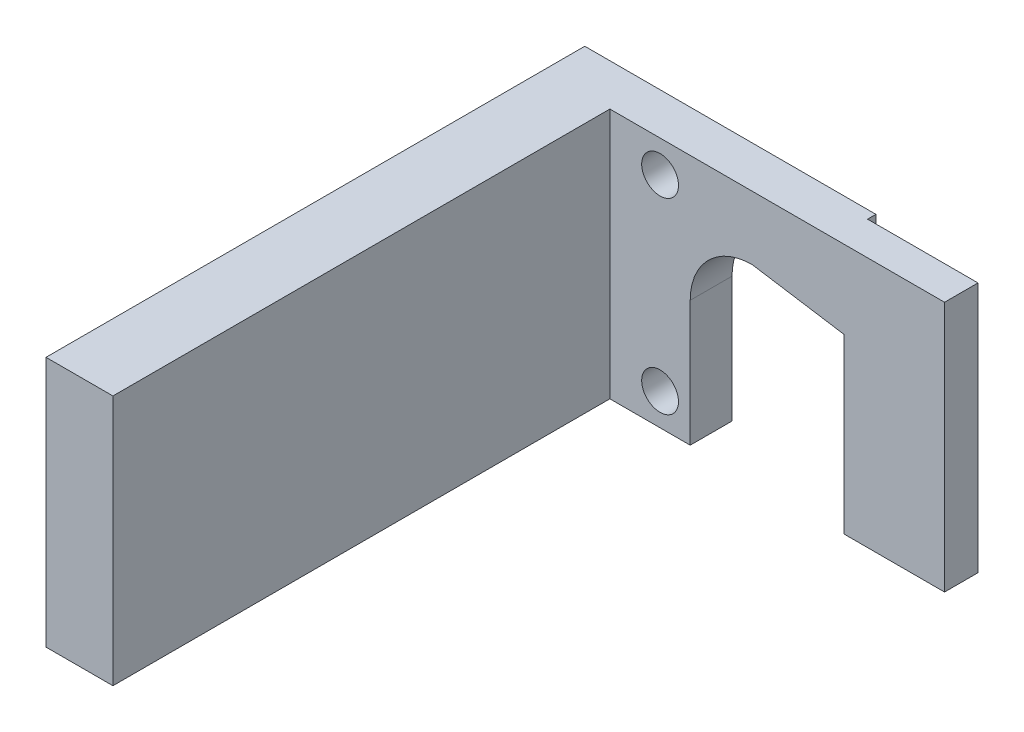
SolidWorks part; units mm, degrees
ref_plane "Front Plane" through (0, 0, 0) normal (0, 0, 1) x (1, 0, 0)
ref_plane "Top Plane" through (0, 0, 0) normal (0, 1, 0) x (1, 0, 0)
ref_plane "Right Plane" through (0, 0, 0) normal (1, 0, 0) x (0, 0, -1)
sketch "Sketch1" plane through (0, 0, 0) normal (0, 0, 1) x (1, 0, 0)
  line L0 (30.48, 9.398) -> (1.27, 9.398) construction
  line L1 (-8.128, 0) -> (-8.128, -19.05)
  line L2 (-30.48, -19.05) -> (-8.128, -19.05)
  line L3 (-30.48, -19.05) -> (-30.48, 19.05)
  line L4 (-30.48, 19.05) -> (30.48, 19.05)
  line L5 (30.48, 9.398) -> (30.48, 19.05)
  line L6 (-30.48, 0) -> (0, 0) construction
  line L7 (1.27, 9.398) -> (15.24, 7.1854)
  line L8 (30.48, 19.05) -> (30.48, 9.398)
  line L11 (30.48, 9.398) -> (30.48, -19.05)
  line L12 (30.48, -19.05) -> (15.24, -19.05)
  line L13 (15.24, 7.1854) -> (15.24, -19.05)
  arc A0 (1.27, 9.398) -> (-8.128, 0) centre (1.27, 0) ccw
  circle A1 centre (-12.7, 14.224) radius 2.794
  circle A2 centre (-12.7, -14.224) radius 2.794
  point P2 (0, 0)
  point P6 (0, 19.05)
  point P16 (-30.48, 0)
  point P21 (25.4, 18.5589)
  point P22 (25.0911, 9.398)
  point P23 (25.4, 9.398)
  dimension "D4" = 9.398
  dimension "D7" = 5.588
  dimension "D1" = 38.1
  dimension "D2" = 60.96
  dimension "D3" = 31.75
  dimension "D5" = 17.78
  dimension "D6" = 4.826
  dimension "D8" = 9
  dimension "D9" = 15.24
extrude "Boss-Extrude1" add sketch "Sketch1" against normal blind 6.35 contours A0 L7 L13 L12 L11 L5 L4 L3 L2 L1 A1 A2 region at (-8.8469, -9.525, 0)
sketch "Sketch4" plane through (0, 19.05, 0) normal (0, 1, 0) x (1, 0, 0)
  line L0 (30.48, 5.08) -> (13.716, 5.08)
  line L1 (30.48, 6.35) -> (30.48, 0) construction
  line L2 (13.716, 5.08) -> (13.716, 6.35)
  line L3 (-30.48, 6.35) -> (30.48, 6.35) construction
  line L4 (30.48, 5.08) -> (30.48, 6.35)
  line L5 (30.48, 6.35) -> (13.716, 6.35)
  dimension "D1" = 16.764
  dimension "D2" = 1.27
extrude "Cut-Extrude3" cut sketch "Sketch4" against normal through all
sketch "Sketch5" plane through (0, 0, 0) normal (0, 0, 1) x (1, 0, 0)
  line L0 (-30.48, 19.05) -> (30.48, 19.05) construction
  line L1 (-30.48, -19.05) -> (-20.32, -19.05)
  line L2 (-30.48, -19.05) -> (-30.48, 19.05)
  line L3 (-30.48, 19.05) -> (-20.32, 19.05)
  line L4 (-20.32, -19.05) -> (-20.32, 19.05)
  dimension "D1" = 10.16
extrude "Boss-Extrude2" add sketch "Sketch5" along normal blind 75.438
